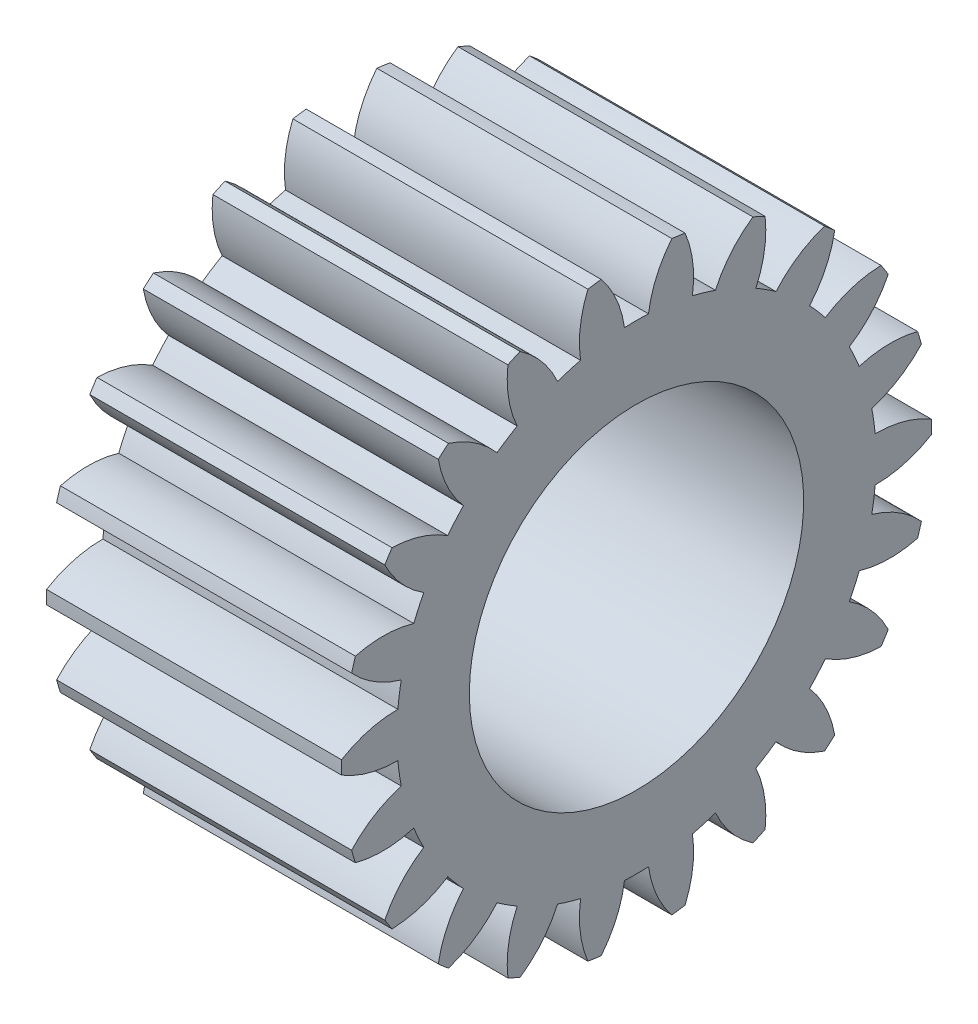
SolidWorks part; units mm, degrees
ref_plane "Plane1" through (0, 0, 0) normal (0, 0, 1) x (1, 0, 0)
ref_plane "Plane2" through (0, 0, 0) normal (0, 1, 0) x (1, 0, 0)
ref_plane "Plane3" through (0, 0, 0) normal (1, 0, 0) x (0, 0, -1)
sketch "HoldingSke" plane through (0, 0, 0) normal (0, 1, 0) x (1, 0, 0)
  line L0 (0, 0) -> (0.7417, -0.2997)
  line L1 (-15, 0) -> (100, 0) construction
  line L2 (0, 0) -> (-2.1039, 2.3779)
  line L3 (0, 0) -> (-11.863, 4.5341)
  line L4 (0, 0) -> (8.0072, 3.2351)
  line L5 (0, 0) -> (-46.8476, -17.4728)
  line L6 (0, 0) -> (-12.4344, -8.3896)
  line L7 (-2.1039, 2.3779) -> (8.6586, 51.2059)
  line L8 (-76.2, 54.61) -> (-73.4, 54.61)
  line L9 (-71.009, 38.7566) -> (-53.1078, 45.2721)
  line L10 (-76.2, 71.12) -> (104.1128, 71.12)
  line L11 (0, 0) -> (-15, 0)
  line L12 (-76.2, 101.6) -> (-76.155, 101.6)
  line L13 (24.9733, 27.94) -> (52.9518, 28.4284)
  line L14 (24.9733, 27.94) -> (24.9743, 27.94)
  line L15 (24.9733, 27.94) -> (100.4006, 29.5858)
  line L16 (-63.627, -1.25) -> (-12.827, -1.25)
  circle A0 centre (0, 0) radius 8.5
  circle A1 centre (0, 0) radius 12.1865
  circle A2 centre (0, 0) radius 37.5
  circle A3 centre (0, 0) radius 8.5
  dimension "Num_teeth" = 22
  dimension "Pitch_radius" = 180.3128
  dimension "Width" = 15
  dimension "Thickness" = 15
sketch "BasProSke" plane through (0, 0, 0) normal (0, 1, 0) x (1, 0, 0)
  line L0 (-10, 0) -> (60, 0) construction
  line L1 (0, 0) -> (0, 15)
  line L2 (0, 0) -> (15, 0)
  line L3 (15, 0) -> (15, 15)
  line L4 (15, 15) -> (0, 15)
  dimension "Thickness" = 15
  dimension "Diameter" = 30
revolve "Base-Revolve" add sketch "BasProSke" angle 360 about L0
sketch "TooCutSke" plane through (0, 0, 0) normal (1, 0, 0) x (0, 0, -1)
  line L1 (0, 0) -> (0, 107) construction
  line L2 (0, 0) -> (-1.0596, 13.7091) construction
  line L3 (0, 0) -> (-3.9052, 27.1614) construction
  line L4 (-1.0596, 13.7091) -> (-1.9526, 13.5807) construction
  arc A0 (0.6099, 12.1712) -> (-0.6099, 12.1712) centre (0, 0) ccw
  arc A1 (1.8166, 14.9152) -> (-1.8166, 14.9152) centre (0, 0) ccw
  circle A2 centre (0, 0) radius 13.75 construction
  circle A3 centre (0, 0) radius 12.9208 construction
  arc A4 (-0.6099, 12.1712) -> (-1.8166, 14.9152) centre (-6.0574, 11.4129) ccw
  arc A5 (1.8166, 14.9152) -> (0.6099, 12.1712) centre (6.0574, 11.4129) ccw
extrude "ToothCut" cut sketch "TooCutSke" along normal through all
fillet "Breaks" [suppressed] radius 0.025 tangent propagation no
fillet "RootFillets" [suppressed] radius 0.3135
pattern_circular "TeethCuts" count 22 every 16.364 about axis through (-10, 0, 0) along (1, 0, 0) of "ToothCut", "RootFillets", "Breaks"
sketch "HubNeaOneSke" plane through (0, 0, 0) normal (-1, 0, 0) x (0, 0, 1)
  circle A0 centre (0, 0) radius 12.1865
  dimension "Diameter" = 24.373
extrude "HubNearOne" [suppressed] add sketch "HubNeaOneSke" along normal blind 35.0001
sketch "HubNeaBotSke" plane through (0, 0, 0) normal (-1, 0, 0) x (0, 0, 1)
  circle A0 centre (0, 0) radius 12.1865
  dimension "Diameter" = 24.373
extrude "HubNearBoth" [suppressed] add sketch "HubNeaBotSke" along normal blind 17.5
ref_plane "FarPln" through (15, 0, 0) normal (1, 0, 0) x (0, 0, -1)
sketch "HubFarSke" plane through (15, 0, 0) normal (1, 0, 0) x (0, 0, -1)
  circle A0 centre (0, 0) radius 12.1865
  dimension "Diameter" = 24.373
extrude "HubFar" [suppressed] add sketch "HubFarSke" along normal blind 17.5
sketch "BorSke" plane through (0, 0, 0) normal (1, 0, 0) x (0, 0, -1)
  circle A0 centre (0, 0) radius 8.5
  dimension "Diameter" = 17
extrude "Bore" cut sketch "BorSke" along normal mid plane 100.0001
sketch "KeySke" plane through (0, 0, 0) normal (1, 0, 0) x (0, 0, -1)
  line L0 (-3, 0) -> (-3, 11.3)
  line L1 (-3, 11.3) -> (3, 11.3)
  line L2 (3, 11.3) -> (3, 0)
  line L3 (0, 0) -> (0, 34) construction
  line L4 (-3, 0) -> (3, 0)
  dimension "Width" = 6
extrude "Keyway" [suppressed] cut sketch "KeySke" along normal mid plane 100.0001
pattern_circular "Keyway2" [suppressed] count 2 every 90 about axis through (-10, 0, 0) along (1, 0, 0) reverse direction yes
equation "' \"Module@HoldingSke\" = 6.35"
equation "' \"Num_teeth@HoldingSke\" = 12"
equation "' \"Ap@HoldingSke\" =  20"
equation "' \"Ap@HoldingSke\" = 20"
equation "' \"Width@HoldingSke\" = 0.5 * 25.4"
equation "' \"Hub_dia@HoldingSke\"= 1 * 25.4"
equation "' \"Hub_dia@HoldingSke\" = 1 * 25.4"
equation "' \"Overall_len@HoldingSke\" = 1.0 * 25.4"
equation "' \"Bore@HoldingSke\" = 0.75 * 25.4"
equation "' \"T_dim@HoldingSke\" = 0.1 * 25.4"
equation "' \"Width@KeySke\" = 0.25 * 25.4"
equation "' \"Show_teeth@HoldingSke\" = 13"
equation "' \"Backlash@HoldingSke\" = 0.009 * 25.4"
equation "' \"Addendum_fac@HoldingSke\" = 1.0"
equation "' \"Dedendum_fac@HoldingSke\" = 1.25"
equation "' \"Dedendum_add@HoldingSke\" = 0.00005 * 25.4"
equation "' \"Clearance_fac@HoldingSke\" = 0.25"
equation "\"Pitch@HoldingSke\" = 1 / \"Module@HoldingSke\""
equation "\"Overcut_dia@TooCutSke\" = (\"Num_teeth@HoldingSke\" + 2 * \"Addendum_fac@HoldingSke\") / \"Pitch@HoldingSke\" + 0.002 * 25.4"
equation "\"Pitch_dia@TooCutSke\" = \"Num_teeth@HoldingSke\" / \"Pitch@HoldingSke\""
equation "\"Base_dia@TooCutSke\" = \"Num_teeth@HoldingSke\" / \"Pitch@HoldingSke\" * cos((\"Ap@HoldingSke\"  * 3.14159265 / 180))"
equation "\"Root_dia@TooCutSke\" = (\"Num_teeth@HoldingSke\" + 2) / \"Pitch@HoldingSke\" - 2 * (\"Addendum_fac@HoldingSke\" + \"Dedendum_fac@HoldingSke\") / \"Pitch@HoldingSke\" - \"Dedendum_add@HoldingSke\" * 2"
equation "\"Half_ang@TooCutSke\" = 180 / \"Num_teeth@HoldingSke\""
equation "\"Half_CT@TooCutSke\" = \"Num_teeth@HoldingSke\" / \"Pitch@HoldingSke\" * sin((3.14159265 / 2 / \"Num_teeth@HoldingSke\")) / 2 - 7 * \"Backlash@HoldingSke\" / 4"
equation "\"Flank_rad@TooCutSke\" = \"Num_teeth@HoldingSke\" / \"Pitch@HoldingSke\" / 5"
equation "\"Radius@RootFillets\" = \"Clearance_fac@HoldingSke\" / \"Pitch@HoldingSke\" + \"Dedendum_add@HoldingSke\""
equation "\"Break_rad@Breaks\" = 0.02 / \"Pitch@HoldingSke\""
equation "\"Thickness@HoldingSke\" = \"Width@HoldingSke\""
equation "\"OAL@HoldingSke\" = \"Thickness@HoldingSke\""
equation "\"MHD@HoldingSke\" = (\"Num_teeth@HoldingSke\" + 2) / \"Pitch@HoldingSke\" - 2 * (\"Addendum_fac@HoldingSke\" + \"Dedendum_fac@HoldingSke\")  / \"Pitch@HoldingSke\" - \"Dedendum_add@HoldingSke\" * 2"
equation "\"MBD@HoldingSke\" = (\"Num_teeth@HoldingSke\" + 2) / \"Pitch@HoldingSke\" - 2 * (\"Addendum_fac@HoldingSke\" + \"Dedendum_fac@HoldingSke\")  / \"Pitch@HoldingSke\" - \"Dedendum_add@HoldingSke\" * 2 - 0.002 * 25.4"
equation "\"MHD@HoldingSke\" = ((sgn( \"MHD@HoldingSke\" - \"Hub_dia@HoldingSke\" )-1)*( \"MHD@HoldingSke\" - \"Hub_dia@HoldingSke\" ))/-2+ \"Hub_dia@HoldingSke\""
equation "\"MBD@HoldingSke\" = ((sgn( \"MBD@HoldingSke\" - \"Bore@HoldingSke\" )-1)*( \"MBD@HoldingSke\" - \"Bore@HoldingSke\" ))/-2+ \"Bore@HoldingSke\""
equation "\"OAL@HoldingSke\" = ((sgn( \"OAL@HoldingSke\" - \"Overall_len@HoldingSke\" )+1)*( \"OAL@HoldingSke\" - \"Overall_len@HoldingSke\" ))/2 + \"Overall_len@HoldingSke\" + 0.000002 * 25.4"
equation "\"Num_teeth@TeethCuts\" = int( \"Show_teeth@HoldingSke\" ) + 1"
equation "\"Num_teeth@TeethCuts\" = ((sgn( \"Num_teeth@TeethCuts\" - \"Num_teeth@HoldingSke\" )-1)*( \"Num_teeth@TeethCuts\" - \"Num_teeth@HoldingSke\" ))/-2+ \"Num_teeth@HoldingSke\""
equation "\"Num_teeth@TeethCuts\" = ((sgn( \"Num_teeth@TeethCuts\" - 2.0)+1)*( \"Num_teeth@TeethCuts\" - 2.0))/2 +2.0"
equation "\"Angle@TeethCuts\" = 360.0 / \"Num_teeth@HoldingSke\""
equation "\"Diameter@BasProSke\" = (\"Num_teeth@HoldingSke\" + 2 * \"Addendum_fac@HoldingSke\") / \"Pitch@HoldingSke\""
equation "\"Thickness@BasProSke\"  = \"Thickness@HoldingSke\""
equation "' \"Fillet_rad@BasProSke\" =  \"Thickness@HoldingSke\" * 0.05"
equation "' \"Fillet_rad@BasProSke\" = \"Thickness@HoldingSke\" * 0.05"
equation "\"MHD@HoldingSke\" = ((sgn( \"MHD@HoldingSke\" - \"Root_dia@TooCutSke\" )-1)*( \"MHD@HoldingSke\" - \"Root_dia@TooCutSke\" ))/-2+ \"Root_dia@TooCutSke\""
equation "\"Diameter@HubNeaOneSke\" = \"MHD@HoldingSke\""
equation "\"Length@HubNearOne\" = \"OAL@HoldingSke\" - \"Thickness@BasProSke\""
equation "\"Diameter@HubNeaBotSke\" = \"MHD@HoldingSke\""
equation "\"Length@HubNearBoth\" = ( \"OAL@HoldingSke\" - \"Thickness@BasProSke\" ) / 2.0"
equation "\"Thickness@FarPln\" = \"Thickness@BasProSke\""
equation "\"Diameter@HubFarSke\" = \"MHD@HoldingSke\""
equation "\"Length@HubFar\" = ( \"OAL@HoldingSke\" - \"Thickness@BasProSke\" ) / 2.0"
equation "\"Diameter@BorSke\" = \"MBD@HoldingSke\""
equation "\"D1@Bore\" = \"OAL@HoldingSke\" * 2.0"
equation "\"D1@Keyway\" = \"OAL@HoldingSke\" * 2.0"
equation "\"Offset@KeySke\" = \"T_dim@HoldingSke\" + \"MBD@HoldingSke\" / 2.0"
